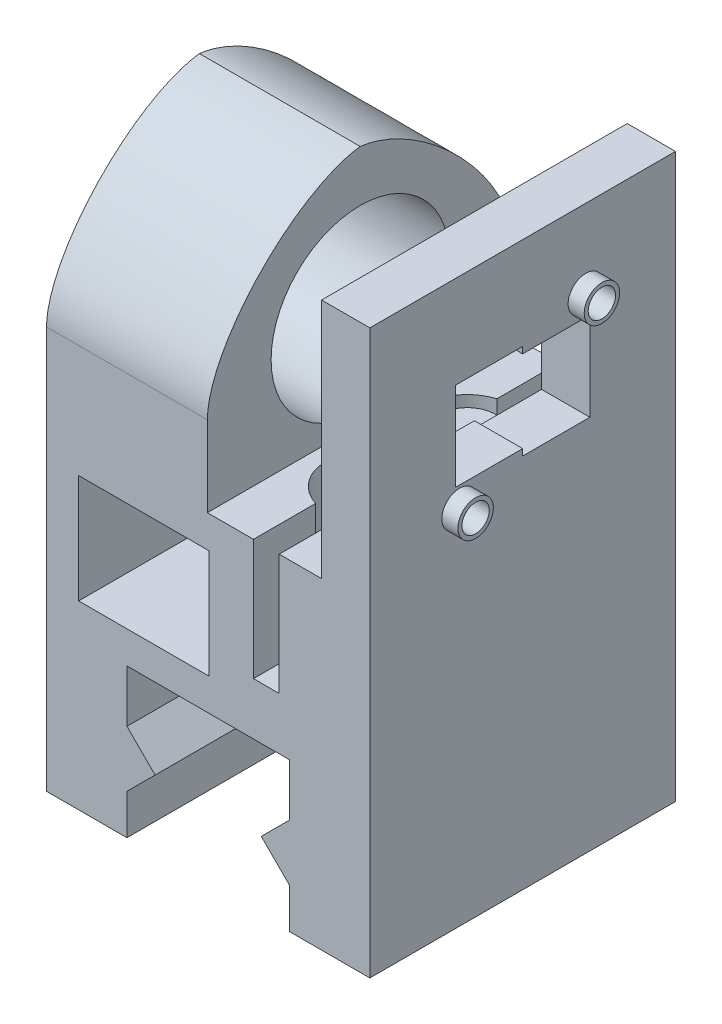
SolidWorks part; units mm, degrees
ref_plane "Front Plane" through (0, 0, 0) normal (0, 0, 1) x (1, 0, 0)
ref_plane "Top Plane" through (0, 0, 0) normal (0, 1, 0) x (1, 0, 0)
ref_plane "Right Plane" through (0, 0, 0) normal (1, 0, 0) x (0, 0, -1)
sketch "Sketch1" plane through (0, 0, 0) normal (0, 0, 1) x (1, 0, 0)
  line L0 (-10.1, 0) -> (10.1, 0)
  line L1 (10.1, 0) -> (10.1, -6.5)
  line L2 (10.1, -6.5) -> (6.6, -10)
  line L3 (6.6, -10) -> (10.1, -10) construction
  line L4 (10.1, -13.5) -> (6.6, -10)
  line L5 (10.1, -13.5) -> (10.1, -18.5)
  line L6 (0, 0) -> (0, -50000) construction
  line L7 (10.1, -18.5) -> (20.1, -18.5)
  line L8 (20.1, -18.5) -> (20.1, 21.5)
  line L9 (20.1, 21.5) -> (-20.1, 21.5)
  line L10 (-6.6, -10) -> (-10.1, -10) construction
  line L11 (-20.1, -18.5) -> (-20.1, 21.5)
  line L12 (-10.1, -18.5) -> (-20.1, -18.5)
  line L13 (-10.1, -13.5) -> (-10.1, -18.5)
  line L14 (-10.1, -13.5) -> (-6.6, -10)
  line L15 (-10.1, -6.5) -> (-6.6, -10)
  line L16 (-10.1, 0) -> (-10.1, -6.5)
  line L18 (-16.1, 17.5) -> (0.1, 17.5)
  line L19 (-16.1, 17.5) -> (-16.1, 4)
  line L20 (-16.1, 4) -> (0.1, 4)
  line L21 (0.1, 17.5) -> (0.1, 4)
  point P16 (0, 21.5)
  point P21 (0, 0)
  dimension "D1" = 10.1
  dimension "D2" = 6.5
  dimension "D3" = 3.5
  dimension "D4" = 45
  dimension "D5" = 5
  dimension "D6" = 10
  dimension "D7" = 40
  dimension "D8" = 4
  dimension "D9" = 4
  dimension "D10" = 20
  dimension "D11" = 4
extrude "Boss-Extrude1" add sketch "Sketch1" along normal mid plane 38
sketch "Sketch2" plane through (0, 21.5, 0) normal (0, 1, 0) x (1, 0, 0)
  line L0 (20.1, -19) -> (-20.1, -19) construction
  line L1 (-20.1, 19) -> (-0.1, 19)
  line L2 (-20.1, 19) -> (-20.1, -19)
  line L3 (-20.1, -19) -> (-0.1, -19)
  line L4 (-0.1, 19) -> (-0.1, -19)
  dimension "D1" = 20
extrude "Boss-Extrude2" add sketch "Sketch2" along normal blind 30
fillet "Fillet2" radius 20 2 edges at (-10.1, 51.5, -19) (-10.1, 51.5, 19) conic rho 0.3
sketch "Sketch7" plane through (0, 21.5, 0) normal (0, 1, 0) x (1, 0, 0)
  line L0 (20.1, 19) -> (-0.1, 19) construction
  line L1 (14.1, 19) -> (20.1, 19)
  line L2 (14.1, 19) -> (14.1, -19)
  line L3 (14.1, -19) -> (20.1, -19)
  line L4 (20.1, 19) -> (20.1, -19)
  dimension "D1" = 6
extrude "Boss-Extrude6" add sketch "Sketch7" along normal blind 30
sketch "Sketch3" plane through (-20.1, 0, 0) normal (-1, 0, 0) x (0, 0, 1)
  line L0 (0, 0) -> (0, 44) construction
  circle A0 centre (0, 34) radius 11.075
  dimension "D1" = 22.15
  dimension "D2" = 34
extrude "Cut-Extrude1" cut sketch "Sketch3" against normal blind 31 and the other way through all
sketch "Sketch9" plane through (20.1, 0, 0) normal (1, 0, 0) x (0, 0, -1)
  line L0 (-19, 51.5) -> (19, 51.5) construction
  line L1 (-19, -18.5) -> (-19, 51.5) construction
  line L4 (-11.6, 45.5) -> (11.6, 45.5) construction
  line L5 (-11.6, 45.5) -> (-11.6, 22.7) construction
  line L6 (-11.6, 22.7) -> (11.6, 22.7) construction
  line L7 (11.6, 45.5) -> (11.6, 22.7) construction
  circle A1 centre (7.85, 41.75) radius 2.2
  circle A2 centre (-7.85, 26.45) radius 2.2
  point P2 (7.85, 41.75)
  point P4 (-7.85, 26.45)
  dimension "D2" = 3.75
  dimension "D3" = 3.75
  dimension "D4" = 3.75
  dimension "D6" = 4.4
  dimension "D5" = 3.75
  dimension "D9" = 22.8
  dimension "D10" = 23.2
  dimension "D11" = 7.4
  dimension "D12" = 6
ref_axis "Axis1" through (-0.1, 34, 0) along (-1, 0, 0)
sketch "Sketch5" plane through (0, 21.5, 0) normal (0, 1, 0) x (1, 0, 0)
  line L0 (14.1, 19) -> (-0.1, 19) construction
  line L1 (17.6, 19) -> (20.1, 19)
  line L2 (17.6, 19) -> (17.6, -19)
  line L3 (17.6, -19) -> (20.1, -19)
  line L4 (20.1, 19) -> (20.1, -19)
  line L5 (14.1, -19) -> (-0.1, -19) construction
  line L6 (20.1, -19) -> (20.1, 19) construction
  dimension "D1" = 2.5
extrude "Boss-Extrude3" add sketch "Sketch5" along normal blind 30
sketch "Sketch11" plane through (0, 21.5, 0) normal (0, 1, 0) x (1, 0, 0)
  line L0 (-0.1, 0) -> (20.1, 0) construction
  line L1 (20.1, -19) -> (20.1, 19) construction
  line L2 (7.23, 19) -> (7.23, -19) construction
  line L3 (5.63, -11.2621) -> (5.63, -19)
  line L4 (8.83, -11.2621) -> (8.83, -19)
  line L5 (5.63, 19) -> (5.63, 11.2621)
  line L6 (8.83, 19) -> (8.83, 11.2621)
  line L7 (5.63, 19) -> (8.83, 19)
  line L8 (5.63, -19) -> (8.83, -19)
  line L11 (1.73, 6) -> (1.73, -6)
  line L12 (12.73, 6) -> (12.73, -6)
  line L13 (14.1, 19) -> (14.1, -19) construction
  circle A0 centre (7.23, 6) radius 3.5
  circle A1 centre (7.23, -6) radius 3.5
  arc A2 (12.73, 6) -> (8.83, 11.2621) centre (7.23, 6) ccw
  arc A3 (8.83, -11.2621) -> (12.73, -6) centre (7.23, -6) ccw
  arc A4 (1.73, -6) -> (5.63, -11.2621) centre (7.23, -6) ccw
  arc A5 (5.63, 11.2621) -> (1.73, 6) centre (7.23, 6) ccw
  dimension "D7" = 7
  dimension "D8" = 11
  dimension "D9" = 11
  dimension "D1" = 38
  dimension "D2" = 3.2
  dimension "D3" = 5.73
  dimension "D4" = 19
  dimension "D5" = 6
  dimension "D6" = 6
  dimension "D10" = 12
  dimension "D11" = 12
extrude "Cut-Extrude5" cut sketch "Sketch11" against normal blind 15
extrude "Boss-Extrude7" add sketch "Sketch9" along normal blind 2
sketch "Sketch19" plane through (20.1, 0, 0) normal (1, 0, 0) x (0, 0, -1)
  line L0 (-19, -18.5) -> (-19, 51.5) construction
  line L1 (-11.6, 45.5) -> (11.6, 45.5) construction
  line L2 (-11.6, 45.5) -> (-11.6, 22.7) construction
  line L3 (-11.6, 22.7) -> (11.6, 22.7) construction
  line L4 (11.6, 45.5) -> (11.6, 22.7) construction
  line L5 (-19, 51.5) -> (19, 51.5) construction
  line L7 (0, 39.2) -> (8.35, 39.2)
  line L8 (0, 29) -> (0, 28.2)
  line L9 (0, 28.2) -> (8.35, 28.2)
  line L10 (8.35, 39.2) -> (8.35, 28.2)
  line L11 (-8.35, 40) -> (0, 40)
  line L12 (-8.35, 40) -> (-8.35, 29)
  line L13 (-8.35, 29) -> (0, 29)
  line L14 (0, 40) -> (0, 39.2)
  dimension "D1" = 23.2
  dimension "D2" = 22.8
  dimension "D3" = 7.4
  dimension "D4" = 6
  dimension "D5" = 11
  dimension "D6" = 8.35
  dimension "D7" = 16.5
  dimension "D8" = 0.8
  dimension "D9" = 11
  dimension "D10" = 8.35
  dimension "D11" = 16.5
  dimension "D12" = 11.6
hole_wizard "M3 Clearance Hole3" positions "3DSketch3" profile "Sketch20" hole size "M3" standard "ANSI Metric"
sketch3d "3DSketch3"
  line L0 (22.1, 41.75, -7.85) -> (20.1, 41.75, -7.85) construction
  line L1 (22.1, 26.45, 7.85) -> (20.1, 26.45, 7.85) construction
  point P0 (22.1, 41.75, -7.85)
  point P4 (22.1, 26.45, 7.85)
sketch "Sketch20" plane through (22.1, 41.75, -7.85) normal (0, 1, 0) x (0, 0, -1)
  line L0 (0, 0) -> (0, 8)
  line L1 (0, 8) -> (1.7, 8)
  line L2 (1.7, 8) -> (1.7, 0)
  line L5 (1.7, 0) -> (0, 0)
  line L10 (0, 8) -> (-1.7, 8) construction
  line L11 (0, -6.35) -> (0, 107.95) construction
  dimension "Hole Dia." = 3.4
  dimension "Hole Depth" = 8
  dimension "Drill Angle" = 180
extrude "Cut-Extrude6" cut sketch "Sketch19" against normal blind 10
